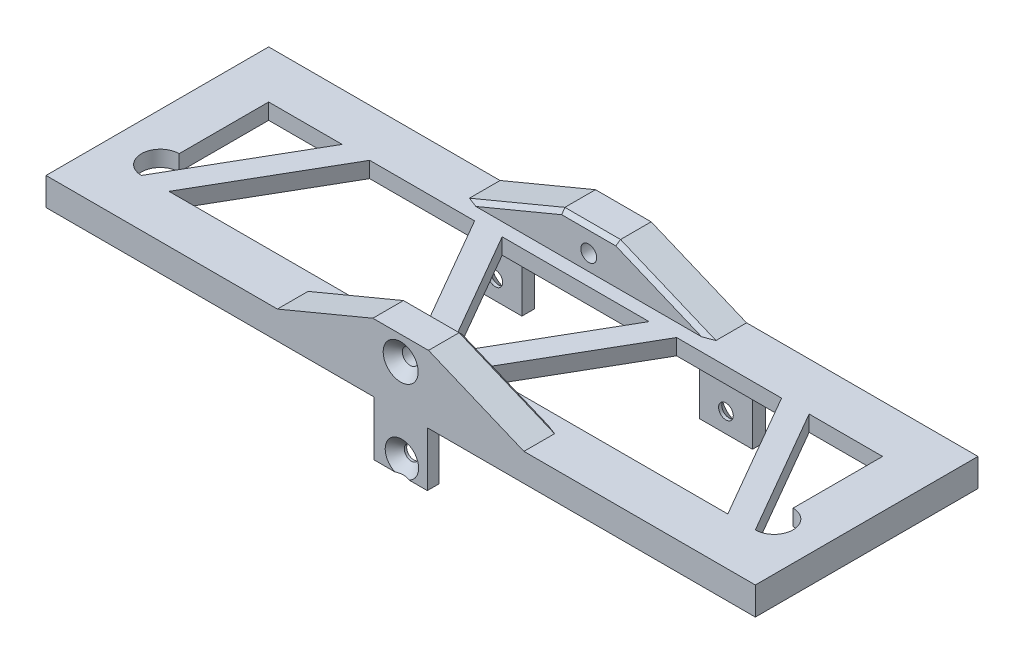
SolidWorks part; units mm, degrees
material "Custom Plastic"
ref_plane "Front Plane" through (0, 0, 0) normal (0, 0, 1) x (1, 0, 0)
ref_plane "Top Plane" through (0, 0, 0) normal (0, 1, 0) x (1, 0, 0)
ref_plane "Right Plane" through (0, 0, 0) normal (1, 0, 0) x (0, 0, -1)
sketch "Sketch1" plane through (0, 0, 0) normal (0, 1, 0) x (1, 0, 0)
  line L0 (-44.6, -14) -> (44.6, -14)
  line L1 (44.6, -14) -> (44.6, 14)
  line L2 (44.6, 14) -> (-44.6, 14)
  line L3 (-44.6, 14) -> (-44.6, -14)
  dimension "D1" = 44.6
  dimension "D2" = 44.6
  dimension "D3" = 14
  dimension "D4" = 14
extrude "Boss-Extrude1" add sketch "Sketch1" along normal blind 2
sketch "Sketch3" plane through (0, 0, 0) normal (0, -1, 0) x (1, 0, 0)
  line L0 (-42.6, 12) -> (-42.6, -12)
  line L1 (-42.6, -12) -> (42.6, -12)
  line L2 (42.6, -12) -> (42.6, 12)
  line L3 (42.6, 12) -> (-42.6, 12)
  line L4 (-44.6, 14) -> (-44.6, -14)
  line L5 (-44.6, -14) -> (44.6, -14)
  line L6 (44.6, -14) -> (44.6, 14)
  line L7 (44.6, 14) -> (-44.6, 14)
  line L8 (-44.6, 14) -> (-44.6, -14)
  line L9 (-44.6, -14) -> (44.6, -14)
  line L10 (44.6, -14) -> (44.6, 14)
  line L11 (44.6, 14) -> (-44.6, 14)
  dimension "D1" = 0
  dimension "D2" = 2
extrude "Boss-Extrude2" add sketch "Sketch3" along normal blind 1.5
ref_plane "Plane1" through (0, 0, 0) normal (1, 0, 0) x (0, 0, -1)
ref_plane "Plane2" through (0, 0, 0) normal (1, 0, 0) x (0, 0, -1)
sketch "Sketch4" plane through (0, 0, 0) normal (0, -1, 0) x (1, 0, 0)
  line L0 (38.6, -8) -> (38.6, 8)
  line L1 (35.1359, 8) -> (3.4641, 8)
  line L2 (-38.6, 8) -> (-38.6, -8)
  line L3 (-38.6, -8) -> (-29.3624, -8)
  line L12 (0, 8) -> (-9.2376, -8)
  line L13 (0, 8) -> (9.2376, -8)
  line L14 (-3.4641, 8) -> (-12.7017, -8)
  line L15 (3.4641, 8) -> (12.7017, -8)
  line L16 (-38.6, 8) -> (-29.3624, -8)
  line L17 (38.6, 8) -> (29.3624, -8)
  line L18 (-35.1359, 8) -> (-25.8983, -8)
  line L19 (35.1359, 8) -> (25.8983, -8)
  line L20 (-25.8983, -8) -> (-12.7017, -8)
  line L21 (-3.4641, 8) -> (-35.1359, 8)
  line L24 (-9.2376, -8) -> (9.2376, -8)
  line L25 (12.7017, -8) -> (25.8983, -8)
  line L26 (29.3624, -8) -> (38.6, -8)
  dimension "D3" = 60
  dimension "D4" = 60
  dimension "D5" = 3
  dimension "D6" = 3
  dimension "D7" = 60
  dimension "D8" = 60
  dimension "D9" = 3
  dimension "D10" = 3
extrude "Cut-Extrude1" cut sketch "Sketch4" against normal up to next
sketch "Sketch5" plane through (0, 2, 0) normal (0, 1, 0) x (1, 0, 0)
  line L0 (44.6, 14) -> (-44.6, 14) construction
  line L1 (-3.5, 14) -> (3.5, 14)
  line L2 (-3.5, 14) -> (-3.5, 9.65)
  line L4 (3.5, 14) -> (3.5, 9.65)
  line L5 (-50.039, 0) -> (57.6591, 0) construction
  line L6 (-3.5, 9.65) -> (3.5, 9.65)
  line L7 (-3.5, -14) -> (-3.5, -9.65)
  line L8 (-3.5, -9.65) -> (3.5, -9.65)
  line L9 (3.5, -14) -> (3.5, -9.65)
  line L10 (-3.5, -14) -> (3.5, -14)
  point P1 (0, 9.65)
  dimension "D1" = 4.35
  dimension "D2" = 7
extrude "Boss-Extrude3" add sketch "Sketch5" along normal blind 5
sketch "Sketch6" plane through (0, 0, 14) normal (0, 0, 1) x (1, 0, 0)
  line L0 (3.5, 7) -> (3.5, 2) construction
  circle A0 centre (0, 4) radius 1
  dimension "D1" = 2
  dimension "D2" = 4
  dimension "D3" = 3.5
extrude "Cut-Extrude2" cut sketch "Sketch6" against normal through all
sketch "Sketch7" plane through (0, 0, 14) normal (0, 0, 1) x (1, 0, 0)
  line L0 (3.5, 7) -> (3.5, 2) construction
  line L1 (-3.5, 7) -> (-3.5, 2) construction
  line L2 (3.5, 7) -> (3.5, 2)
  line L3 (-3.5, 7) -> (-3.5, 2)
  line L4 (-3.5, 7) -> (-15.5, 2)
  line L5 (-44.6, 2) -> (-3.5, 2) construction
  line L6 (-15.5, 2) -> (-3.5, 2)
  line L7 (3.5, 7) -> (15.5, 2)
  line L8 (3.5, 2) -> (44.6, 2) construction
  line L9 (15.5, 2) -> (3.5, 2)
  dimension "D1" = 12
  dimension "D2" = 12
extrude "Boss-Extrude4" add sketch "Sketch7" against normal up to surface (4.35 mm away) up to face at (1, 4, 9.65)
ref_plane "Plane3" through (0, 0, 0) normal (0, 0, 1) x (1, 0, 0)
sketch "Sketch8" plane through (0, 0, -14) normal (0, 0, -1) x (-1, 0, 0)
  line L0 (3.5, 7) -> (3.5, 2) construction
  line L1 (3.5, 7) -> (3.5, 2)
  line L2 (-3.5, 7) -> (-3.5, 2) construction
  line L3 (-3.5, 7) -> (-3.5, 2)
  line L4 (-3.5, 7) -> (-15.5, 2)
  line L5 (-15.5, 2) -> (-3.5, 2)
  line L6 (3.5, 2) -> (15.5, 2)
  line L7 (15.5, 2) -> (3.5, 7)
extrude "Boss-Extrude5" add sketch "Sketch8" against normal up to surface (4.35 mm away) up to face at (-1, 4, -9.65)
chamfer "Chamfer1" distance 1.2 angle 45 1 edges at (1, 4, -14)
chamfer "Chamfer2" distance 1.2 angle 45 1 edges at (1, 4, 14)
sketch "Sketch9" plane through (0, 0, 14) normal (0, 0, 1) x (1, 0, 0)
  line L2 (-3.5, -8.5) -> (3.5, -8.5) construction
  line L6 (44.6, -1.5) -> (-44.6, -1.5) construction
  line L7 (3.35, -1.5) -> (-3.35, -1.5)
  line L8 (-3.35, -1.5) -> (-3.35, -8.35)
  line L9 (-3.35, -8.35) -> (3.35, -8.35)
  line L10 (3.35, -8.35) -> (3.35, -1.5)
  line L11 (-3.5, -1.5) -> (-3.5, -8.5) construction
  line L12 (3.5, -8.5) -> (3.5, -1.5) construction
  dimension "D1" = 0.15
  dimension "D2" = 0.15
  dimension "D3" = 0.15
extrude "Boss-Extrude6" add sketch "Sketch9" against normal blind 1.5
sketch "Sketch15" plane through (0, -1.5, 0) normal (0, -1, 0) x (1, 0, 0)
  line L1 (18, -14) -> (11, -14) construction
  line L5 (-11, -14) -> (-18, -14) construction
  line L9 (17.85, -14) -> (11.15, -14)
  line L13 (-11.15, -14) -> (-17.85, -14)
  line L16 (-17.85, -14) -> (-17.85, -12.4)
  line L17 (-11.15, -12.4) -> (-11.15, -14)
  line L18 (11.15, -14) -> (11.15, -12.4)
  line L19 (17.85, -12.4) -> (17.85, -14)
  line L20 (11.15, -12.4) -> (17.85, -12.4)
  line L21 (-17.85, -12.4) -> (-11.15, -12.4)
  line L22 (-18, -12.25) -> (-18, -14) construction
  line L23 (-11, -12.25) -> (-11, -14) construction
  point P4 (-17.85, -12.25)
  point P6 (-11.15, -12.25)
  point P8 (-11, -12.25)
  point P13 (-18, -12.25)
  point P18 (-18, -12.4)
  point P19 (-11, -12.4)
  dimension "D1" = 1.6
  dimension "D2" = 6.7
  dimension "D3" = 1.6
  dimension "D4" = 0.15
  dimension "D5" = 0.15
  dimension "D6" = 1.6
  dimension "D7" = 22.3
  dimension "D8" = 6.7
  dimension "D9" = 11.15
extrude "Boss-Extrude7" add sketch "Sketch15" along normal offset from surface (8.3 mm away) 0.2
sketch "Sketch16" plane through (0, 0, -14) normal (0, 0, -1) x (-1, 0, 0)
  circle A0 centre (14.5, -7.35) radius 0.925 construction
  circle A1 centre (-14.5, -7.35) radius 0.925 construction
  circle A2 centre (14.5, -7.35) radius 0.925
  circle A3 centre (-14.5, -7.35) radius 0.925
extrude "Cut-Extrude9" cut sketch "Sketch16" against normal up to next
sketch "Sketch17" plane through (0, 0, 14) normal (0, 0, 1) x (1, 0, 0)
  circle A2 centre (0.1553, -6.45) radius 0.9 construction
  circle A3 centre (0.1553, -6.45) radius 0.9
extrude "Cut-Extrude11" cut sketch "Sketch17" against normal up to next
chamfer "Chamfer3" distance 1.2 angle 45 1 edges at (1.0553, -6.45, 14)
chamfer "Chamfer4" distance 1.2 angle 45 2 edges at (13.575, -7.35, -14) (-15.425, -7.35, -14)
sketch "Sketch18" plane through (0, 0, 0) normal (0, -1, 0) x (1, 0, 0)
  line L0 (38.6, -8) -> (38.6, 8) construction
  line L3 (-38.6, 8) -> (-38.6, -8) construction
  line L4 (38.6, 3.26) -> (38.6, 8)
  line L7 (-38.6, 8) -> (-38.6, 3.2579)
  arc A0 (-38.6, 8) -> (-38.6, 3.2579) centre (-38.6, 5.629) ccw
  arc A1 (38.6, 3.26) -> (38.6, 8) centre (38.6, 5.63) ccw
  point P8 (0, 0)
  point P9 (0, 0)
  point P10 (0, 0)
  dimension "D1" = 4.7421
  dimension "D2" = 4.74
extrude "Cut-Extrude12" cut sketch "Sketch18" against normal through all
chamfer "Chamfer5" distance 0.5 angle 45 3 edges at (9.5, 4.5, -9.65) (0, 7, -9.65) (-9.5, 4.5, -9.65)
chamfer "Chamfer6" distance 0.5 angle 45 3 edges at (9.5, 4.5, 9.65) (0, 7, 9.65) (-9.5, 4.5, 9.65)
